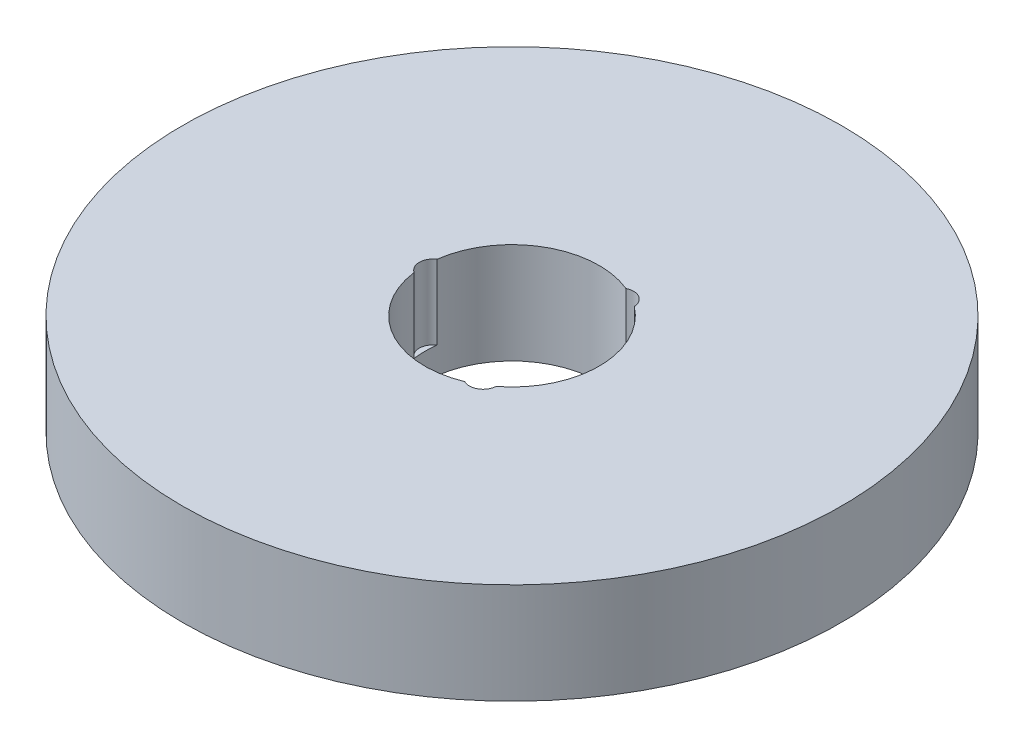
SolidWorks part; units mm, degrees
ref_plane "Front Plane" through (0, 0, 0) normal (0, 0, 1) x (1, 0, 0)
ref_plane "Top Plane" through (0, 0, 0) normal (0, 1, 0) x (1, 0, 0)
ref_plane "Right Plane" through (0, 0, 0) normal (1, 0, 0) x (0, 0, -1)
sketch "Sketch1" plane through (0, 0, 0) normal (0, 1, 0) x (1, 0, 0)
  circle A0 centre (0, 0) radius 85
  dimension "FLANGE_OD" = 170
extrude "Boss-Extrude1" add sketch "Sketch1" along normal blind 26
sketch "Sketch2" plane through (0, 0, 0) normal (0, 1, 0) x (1, 0, 0)
  circle A0 centre (0, 0) radius 22.5
  dimension "BORE_D" = 45
extrude "Cut-Extrude1" cut sketch "Sketch2" along normal through all
sketch "Sketch3" plane through (0, 26, 0) normal (0, 1, 0) x (1, 0, 0)
  circle A0 centre (0, 0) radius 20.3856 construction
  circle A1 centre (-20.3856, 0) radius 3.52
  dimension "BOLT_D" = 7.04
  dimension "BOLT_PCD" = 40.7712
extrude "Cut-Extrude2" cut sketch "Sketch3" against normal blind 19.1836
pattern_circular "CirPattern1" count 3 over 360 about axis through (0, 0, 0) along (0, 1, 0) of "Cut-Extrude2"
